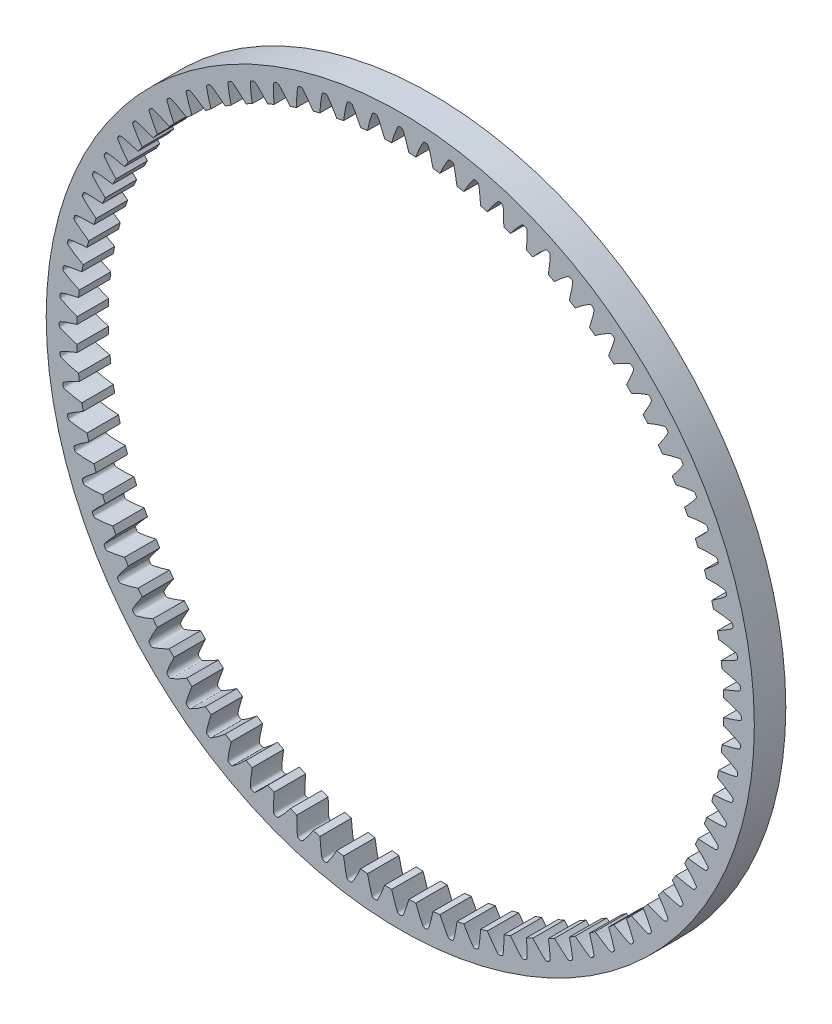
SolidWorks part; units mm, degrees
ref_plane "Front Plane" through (0, 0, 0) normal (0, 0, 1) x (1, 0, 0)
ref_plane "Top Plane" through (0, 0, 0) normal (0, 1, 0) x (1, 0, 0)
ref_plane "Right Plane" through (0, 0, 0) normal (1, 0, 0) x (0, 0, -1)
ref_axis "Axis1" through (0, 0, 55) along (0, 0, -1)
sketch "SketchRevolveSpurGear" plane through (0, 0, 0) normal (1, 0, 0) x (0, 0, -1)
  line L0 (0, 0) -> (1, 0) construction
  line L1 (-2, 41.1) -> (-2, 45)
  line L2 (-2, 45) -> (2, 45)
  line L3 (2, 45) -> (2, 41.1)
  line L4 (2, 41.1) -> (-2, 41.1)
  dimension "Side1" = 2
  dimension "OutsideRadius" = 45
  dimension "Side2" = 2
  dimension "MinorDiameter" = 41.1
revolve "SpurGear" add sketch "SketchRevolveSpurGear" angle 360 about L0
sketch "SketchToothSpurGear" plane through (0, 0, 0) normal (0, 0, 1) x (1, 0, 0)
  arc A0 (41.0533, -1.1048) -> (41.0533, 1.1048) centre (0, 0) ccw
  spline S0 degree 3 poles (41.0533, 1.1048) (41.1734, 1.0737) (41.3575, 1.0228) (41.6074, 0.9476) (41.8076, 0.884) (42.0159, 0.8142) (42.232, 0.738) (42.4558, 0.655) (42.6875, 0.5656) (42.9257, 0.467) (43.1025, 0.3975) (43.2091, 0.3451) (43.2445, 0.3189) (43.2757, 0.2884) (43.3021, 0.2537) (43.3232, 0.2156) (43.3437, 0.1616) (43.3509, 0.1033) (43.3498, 0.045) (43.3501, 0) (43.3498, -0.045) (43.3509, -0.1033) (43.3437, -0.1616) (43.3232, -0.2156) (43.3021, -0.2537) (43.2757, -0.2884) (43.2445, -0.3189) (43.2091, -0.3451) (43.1025, -0.3975) (42.9257, -0.467) (42.6875, -0.5656) (42.4558, -0.655) (42.232, -0.738) (42.0159, -0.8142) (41.8076, -0.884) (41.6074, -0.9476) (41.3575, -1.0228) (41.1734, -1.0737) (41.0533, -1.1048) knots 0 0 0 0 0.069441 0.106833 0.146006 0.18696 0.229694 0.27421 0.320506 0.368584 0.418442 0.426778 0.434883 0.442987 0.451092 0.459196 0.467301 0.483237 0.491619 0.5 0.508381 0.516763 0.532699 0.540804 0.548908 0.557013 0.565117 0.573222 0.581558 0.631416 0.679494 0.72579 0.770306 0.81304 0.853994 0.893167 0.930559 1 1 1 1
extrude "ToothExtrudeCutSpurGear" cut sketch "SketchToothSpurGear" against normal blind 2 and the other way blind 2
pattern_circular "PatternSpurGear" count 84 every 4.286 about axis through (0, 0, 55) along (0, 0, -1) of "ToothExtrudeCutSpurGear"
sketch "AuxiliarySketchSpurGear" plane through (0, 0, 0) normal (0, 0, 1) x (1, 0, 0)
  circle A0 centre (0, 0) radius 42 construction
  circle A1 centre (0, 0) radius 39.4671 construction
  circle A2 centre (0, 0) radius 43.35 construction
  circle A3 centre (0, 0) radius 41.1 construction
  dimension "PitchDiameter" = 84
  dimension "BaseDiameter" = 78.9342
  dimension "MajorDiameter" = 86.7
  dimension "MinorDiameter" = 82.2
